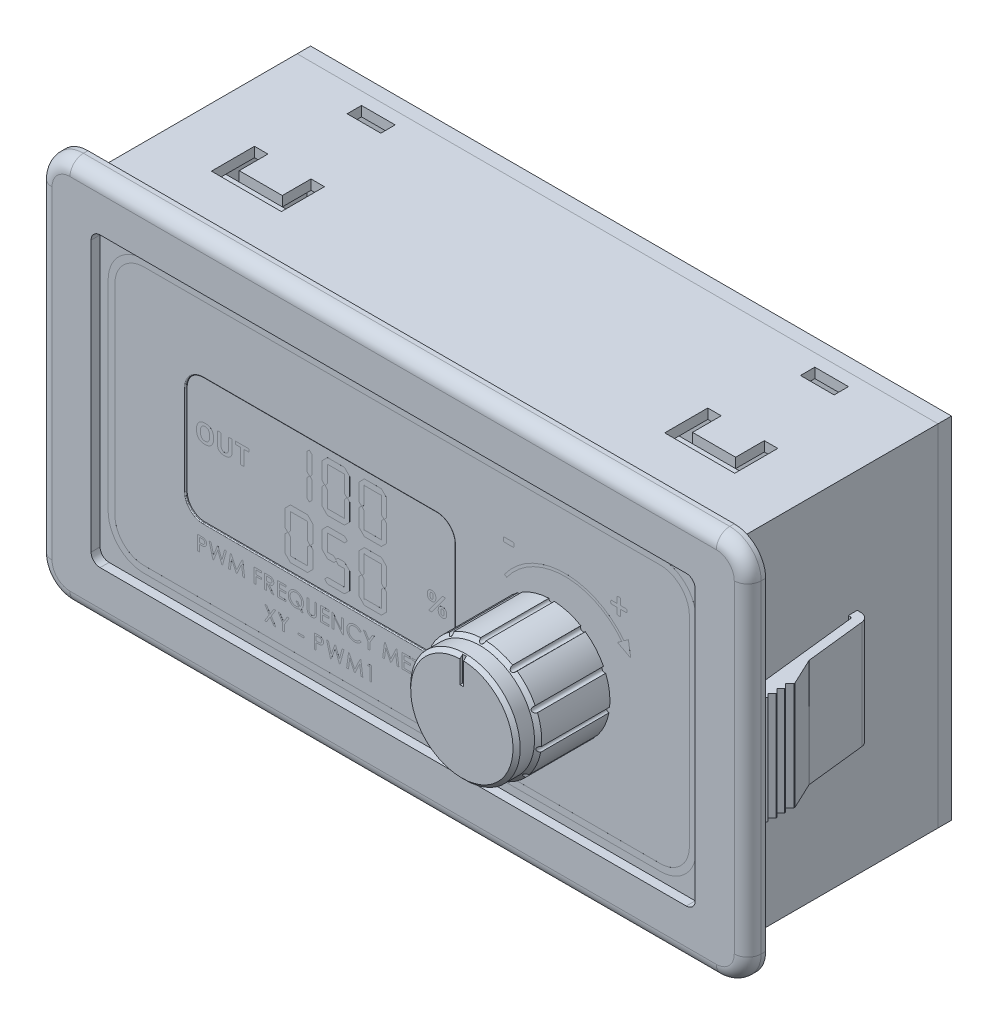
SolidWorks part; units mm, degrees
other "Case"
other "Back Cover"
other "PCB"
other "Rotary Encoder"
other "Connection"
material "ABS"
ref_plane "Front Plane" through (0, 0, 0) normal (0, 0, 1) x (1, 0, 0)
ref_plane "Top Plane" through (0, 0, 0) normal (0, 1, 0) x (1, 0, 0)
ref_plane "Right Plane" through (0, 0, 0) normal (1, 0, 0) x (0, 0, -1)
sketch "Sketch1" plane through (0, 0, 0) normal (0, 0, 1) x (1, 0, 0)
  line L1 (-39.5, 21.5) -> (39.5, 21.5)
  line L2 (-39.5, 21.5) -> (-39.5, -21.5)
  line L3 (-39.5, -21.5) -> (39.5, -21.5)
  line L4 (39.5, 21.5) -> (39.5, -21.5)
  line L5 (-39.5, 21.5) -> (39.5, -21.5) construction
  line L6 (-39.5, -21.5) -> (39.5, 21.5) construction
  point P0 (0, 0)
  dimension "D1" = 79
  dimension "D2" = 43
extrude "Boss-Extrude1" add sketch "Sketch1" along normal blind 2
sketch "Sketch2" plane through (0, 0, 0) normal (0, 0, -1) x (-1, 0, 0)
  line L1 (-35.7, 19.5) -> (35.7, 19.5)
  line L2 (-35.7, 19.5) -> (-35.7, -19.5)
  line L3 (-35.7, -19.5) -> (35.7, -19.5)
  line L4 (35.7, 19.5) -> (35.7, -19.5)
  line L5 (-35.7, 19.5) -> (35.7, -19.5) construction
  line L6 (-35.7, -19.5) -> (35.7, 19.5) construction
  point P0 (0, 0)
  dimension "D1" = 39
  dimension "D2" = 71.4
extrude "Boss-Extrude2" add sketch "Sketch2" along normal blind 23
sketch "Sketch3" plane through (0, 0, 2) normal (0, 0, 1) x (1, 0, 0)
  line L1 (-33.65, 16.05) -> (33.65, 16.05)
  line L2 (-33.65, 16.05) -> (-33.65, -16.05)
  line L3 (-33.65, -16.05) -> (33.65, -16.05)
  line L4 (33.65, 16.05) -> (33.65, -16.05)
  line L5 (-33.65, 16.05) -> (33.65, -16.05) construction
  line L6 (-33.65, -16.05) -> (33.65, 16.05) construction
  point P0 (0, 0)
  dimension "D1" = 67.3
  dimension "D2" = 32.1
extrude "Cut-Extrude1" cut sketch "Sketch3" against normal blind 1
sketch "Sketch4" plane through (0, 0, -23) normal (0, 0, -1) x (-1, 0, 0)
  line L0 (35.7, 19.5) -> (-35.7, 19.5) construction
  line L1 (-34.6, 18.4) -> (34.6, 18.4)
  line L2 (-34.6, 18.4) -> (-34.6, -18.4)
  line L3 (-34.6, -18.4) -> (34.6, -18.4)
  line L4 (34.6, 18.4) -> (34.6, -18.4)
  line L5 (-34.6, 18.4) -> (34.6, -18.4) construction
  line L6 (-34.6, -18.4) -> (34.6, 18.4) construction
  line L7 (-35.7, 19.5) -> (-35.7, -19.5) construction
  point P0 (0, 0)
  dimension "D1" = 1.1
  dimension "D2" = 1.1
extrude "Cut-Extrude2" cut sketch "Sketch4" against normal up to surface (23 mm away) up to face at (0, 0, 0)
sketch "Sketch5" plane through (0, 0, 1) normal (0, 0, 1) x (1, 0, 0)
  line L0 (0, 0) -> (18.15, 0) construction
  line L1 (18.15, 0) -> (33.65, 0) construction
  line L3 (33.65, -16.05) -> (33.65, 16.05) construction
  line L4 (33.65, 0) -> (39.5, 0) construction
  line L5 (39.5, -21.5) -> (39.5, 21.5) construction
  circle A0 centre (18.15, 0) radius 3.5
  dimension "D1" = 7
  dimension "D2" = 15.5
extrude "Cut-Extrude3" cut sketch "Sketch5" against normal up to surface (1 mm away) up to face at (0, 0, 0)
sketch "Sketch6" plane through (0, -19.5, 0) normal (0, -1, 0) x (1, 0, 0)
  line L0 (0, 0) -> (0, -8.5) construction
  line L1 (35.7, -23) -> (-35.7, -23) construction
  line L2 (-8.6, -8.5) -> (8.6, -8.5)
  line L3 (-11.1, -11) -> (-11.1, -23)
  line L4 (-11.1, -23) -> (11.1, -23)
  line L5 (11.1, -11) -> (11.1, -23)
  line L6 (-25.25, 0) -> (25.25, 0) construction
  line L7 (35.7, 0) -> (-35.7, 0) construction
  line L8 (25.25, 0) -> (25.25, -6.9) construction
  line L9 (-25.25, 0) -> (-25.25, -6.9) construction
  line L10 (21.35, -6.9) -> (29.15, -6.9)
  line L11 (-29.15, -6.9) -> (-21.35, -6.9)
  line L12 (-25.25, -6.9) -> (-25.25, -8.5) construction
  line L13 (25.25, -6.9) -> (25.25, -8.5) construction
  line L14 (22.85, -8.5) -> (27.65, -8.5)
  line L15 (-27.65, -8.5) -> (-22.85, -8.5)
  line L16 (-29.15, -6.9) -> (-29.15, -11.7)
  line L17 (-29.15, -11.7) -> (-27.65, -11.7)
  line L18 (-27.65, -11.7) -> (-27.65, -8.5)
  line L19 (-22.85, -8.5) -> (-22.85, -11.7)
  line L20 (-22.85, -11.7) -> (-21.35, -11.7)
  line L21 (-21.35, -11.7) -> (-21.35, -6.9)
  line L22 (29.15, -6.9) -> (29.15, -11.7)
  line L23 (29.15, -11.7) -> (27.65, -11.7)
  line L24 (27.65, -11.7) -> (27.65, -8.5)
  line L25 (22.85, -8.5) -> (22.85, -11.7)
  line L26 (22.85, -11.7) -> (21.35, -11.7)
  line L27 (21.35, -11.7) -> (21.35, -6.9)
  line L28 (-25.25, -8.5) -> (-25.25, -20.8) construction
  line L29 (-25.25, -20.8) -> (-25.25, -23) construction
  line L30 (-27.125, -20) -> (-23.375, -20)
  line L31 (-27.125, -20) -> (-27.125, -21.6)
  line L32 (-27.125, -21.6) -> (-23.375, -21.6)
  line L33 (-23.375, -20) -> (-23.375, -21.6)
  line L34 (-27.125, -20) -> (-23.375, -21.6) construction
  line L35 (-27.125, -21.6) -> (-23.375, -20) construction
  line L36 (25.25, -8.5) -> (25.25, -20.8) construction
  line L37 (25.25, -20.8) -> (25.25, -23) construction
  line L39 (23.375, -20) -> (27.125, -20)
  line L40 (23.375, -20) -> (23.375, -21.6)
  line L41 (23.375, -21.6) -> (27.125, -21.6)
  line L42 (27.125, -20) -> (27.125, -21.6)
  line L43 (23.375, -20) -> (27.125, -21.6) construction
  line L44 (23.375, -21.6) -> (27.125, -20) construction
  arc A0 (-8.6, -8.5) -> (-11.1, -11) centre (-8.6, -11) ccw
  arc A1 (8.6, -8.5) -> (11.1, -11) centre (8.6, -11) cw
  dimension "D3" = 2.5
  dimension "D1" = 22.2
  dimension "D2" = 8.5
  dimension "D4" = 50.5
  dimension "D6" = 4.8
  dimension "D7" = 7.8
  dimension "D8" = 1.6
  dimension "D9" = 4.8
  dimension "D10" = 3.75
  dimension "D11" = 1.6
  dimension "D12" = 3
extrude "Cut-Extrude4" cut sketch "Sketch6" against normal up to surface (1.1 mm away) up to face at (0, -18.4, -11.5)
sketch "Sketch7" plane through (0, 19.5, 0) normal (0, 1, 0) x (1, 0, 0)
  line L0 (21.35, 11.7) -> (21.35, 6.9) construction
  line L1 (22.85, 11.7) -> (21.35, 11.7) construction
  line L2 (22.85, 8.5) -> (22.85, 11.7) construction
  line L3 (29.15, 6.9) -> (29.15, 11.7) construction
  line L4 (29.15, 11.7) -> (27.65, 11.7) construction
  line L5 (27.65, 11.7) -> (27.65, 8.5) construction
  line L6 (22.85, 8.5) -> (27.65, 8.5) construction
  line L7 (21.35, 6.9) -> (29.15, 6.9) construction
  line L8 (21.35, 11.7) -> (21.35, 6.9)
  line L9 (22.85, 11.7) -> (21.35, 11.7)
  line L10 (22.85, 8.5) -> (22.85, 11.7)
  line L11 (29.15, 6.9) -> (29.15, 11.7)
  line L12 (29.15, 11.7) -> (27.65, 11.7)
  line L13 (27.65, 11.7) -> (27.65, 8.5)
  line L14 (22.85, 8.5) -> (27.65, 8.5)
  line L15 (21.35, 6.9) -> (29.15, 6.9)
  line L16 (-29.15, 11.7) -> (-27.65, 11.7) construction
  line L17 (-22.85, 11.7) -> (-21.35, 11.7) construction
  line L18 (-22.85, 8.5) -> (-22.85, 11.7) construction
  line L19 (-27.65, 11.7) -> (-27.65, 8.5) construction
  line L20 (-29.15, 6.9) -> (-29.15, 11.7) construction
  line L21 (-21.35, 11.7) -> (-21.35, 6.9) construction
  line L22 (-27.65, 8.5) -> (-22.85, 8.5) construction
  line L23 (-29.15, 6.9) -> (-21.35, 6.9) construction
  line L24 (-29.15, 11.7) -> (-27.65, 11.7)
  line L25 (-22.85, 11.7) -> (-21.35, 11.7)
  line L26 (-22.85, 8.5) -> (-22.85, 11.7)
  line L27 (-27.65, 11.7) -> (-27.65, 8.5)
  line L28 (-29.15, 6.9) -> (-29.15, 11.7)
  line L29 (-21.35, 11.7) -> (-21.35, 6.9)
  line L30 (-27.65, 8.5) -> (-22.85, 8.5)
  line L31 (-29.15, 6.9) -> (-21.35, 6.9)
  line L32 (-27.125, 20) -> (-27.125, 21.6) construction
  line L33 (-27.125, 20) -> (-23.375, 20) construction
  line L34 (-23.375, 20) -> (-23.375, 21.6) construction
  line L35 (-27.125, 21.6) -> (-23.375, 21.6) construction
  line L36 (-27.125, 20) -> (-27.125, 21.6)
  line L37 (-27.125, 20) -> (-23.375, 20)
  line L38 (-23.375, 20) -> (-23.375, 21.6)
  line L39 (-27.125, 21.6) -> (-23.375, 21.6)
  line L40 (23.375, 20) -> (23.375, 21.6) construction
  line L41 (23.375, 20) -> (27.125, 20) construction
  line L42 (27.125, 20) -> (27.125, 21.6) construction
  line L43 (23.375, 21.6) -> (27.125, 21.6) construction
  line L44 (23.375, 20) -> (23.375, 21.6)
  line L45 (23.375, 20) -> (27.125, 20)
  line L46 (27.125, 20) -> (27.125, 21.6)
  line L47 (23.375, 21.6) -> (27.125, 21.6)
extrude "Cut-Extrude5" cut sketch "Sketch7" against normal up to surface (1.1 mm away) up to face at (0, 18.4, -11.5)
sketch "Sketch8" plane through (0, 0, 0) normal (0, 1, 0) x (1, 0, 0)
  line L0 (0, 0) -> (0, 14) construction
  line L1 (-35.7, 14) -> (35.7, 14) construction
  line L2 (35.7, 23) -> (35.7, 0) construction
  line L3 (-35.7, 14) -> (-37, 14)
  line L4 (35.7, 14) -> (37, 14)
  line L5 (-35.7, 14) -> (-35.7, 13)
  line L6 (-35.7, 23) -> (-35.7, 0) construction
  line L7 (35.7, 14) -> (35.7, 13)
  line L8 (-35.7, 13) -> (-36.1054, 13)
  line L9 (35.7, 13) -> (36.1054, 13)
  line L10 (-36.1054, 13) -> (-37.5, 0.5)
  line L11 (-37.5, 0.5) -> (-39.25, 0.5)
  line L12 (-37.5, 0.5) -> (-37.5, 0) construction
  line L13 (39.5, 0) -> (-39.5, 0) construction
  line L14 (36.1054, 13) -> (37.5, 0.5)
  line L15 (37.5, 0.5) -> (37.5, 0) construction
  line L16 (-37.5, 0) -> (-35.7, 0) construction
  line L17 (37.5, 0) -> (35.7, 0) construction
  line L18 (37.5, 0.5) -> (39.25, 0.5)
  line L19 (-39.25, 0.5) -> (-39.25, 3.5)
  line L20 (-37, 14) -> (-37.8368, 6.5)
  line L21 (-37.8368, 6.5) -> (-39.25, 3.5)
  line L22 (39.25, 0.5) -> (39.25, 3.5)
  line L23 (37, 14) -> (37.8368, 6.5)
  line L24 (37.8368, 6.5) -> (39.25, 3.5)
  dimension "D1" = 14
  dimension "D2" = 74
  dimension "D3" = 1
  dimension "D4" = 0.5
  dimension "D5" = 75
  dimension "D6" = 3
  dimension "D7" = 6.5
  dimension "D8" = 6.5
  dimension "D9" = 78.5
  dimension "D10" = 1
extrude "Boss-Extrude3" add sketch "Sketch8" along normal mid plane 12
fillet "Fillet1" radius 1 2 edges at (37, 0, -14) (-37, 0, -14)
fillet "Fillet2" radius 0.2 6 edges at (36.1054, 0, -13) (-36.1054, 0, -13) (39.25, 0, -3.5) (37.8368, 0, -6.5) (-39.25, 0, -3.5) (-37.8368, 0, -6.5)
sketch "Sketch9" plane through (0, 6, 0) normal (0, 1, 0) x (1, 0, 0)
  line L0 (-39.25, 3.4553) -> (-38.7575, 2.9627)
  line L1 (-38.7575, 2.9627) -> (-39.25, 2.4702)
  line L2 (-39.25, 3.4553) -> (-39.25, 0.5) construction
  line L3 (-39.25, 2.4702) -> (-38.7575, 1.9776)
  line L4 (-38.7575, 1.9776) -> (-39.25, 1.4851)
  line L5 (-39.25, 1.4851) -> (-38.7575, 0.9925)
  line L6 (-38.7575, 0.9925) -> (-39.25, 0.5)
  line L7 (-39.25, 3.4553) -> (-40.25, 3.4553)
  line L8 (-40.25, 3.4553) -> (-40.25, 0.5)
  line L9 (-40.25, 0.5) -> (-39.25, 0.5)
  line L10 (-39.25, 0.5) -> (-37.5, 0.5) construction
  line L11 (-38.7575, 0.9925) -> (-39.25, 0.9925) construction
  line L12 (-39.25, 1.4851) -> (-39.25, 0.5) construction
  line L13 (39.25, 0.5) -> (40.25, 0.5)
  line L14 (40.25, 0.5) -> (40.25, 3.4553)
  line L15 (40.25, 3.4553) -> (39.25, 3.4553)
  line L16 (39.25, 0.5) -> (39.25, 1.4851) construction
  line L17 (39.25, 0.5) -> (39.25, 3.4553) construction
  line L18 (39.25, 0.9925) -> (38.7575, 0.9925) construction
  line L19 (39.25, 0.5) -> (38.7575, 0.9925)
  line L20 (38.7575, 0.9925) -> (39.25, 1.4851)
  line L21 (39.25, 1.4851) -> (38.7575, 1.9776)
  line L22 (38.7575, 1.9776) -> (39.25, 2.4702)
  line L23 (39.25, 2.4702) -> (38.7575, 2.9627)
  line L24 (38.7575, 2.9627) -> (39.25, 3.4553)
  line L25 (39.25, 2.4702) -> (39.25, 3.4553) construction
  line L26 (-39.25, 2.4702) -> (-39.25, 3.4553) construction
  dimension "D1" = 1
extrude "Cut-Extrude6" cut sketch "Sketch9" against normal up to surface (12 mm away) up to face at (-37.3148, -6, -8.43)
fillet "Fillet3" radius 0.1 8 edges at (39.25, 0, -3.4553) (39.25, 0, -2.4702) (39.25, 0, -1.4851) (39.25, 0, -0.5) (-39.25, 0, -3.4553) (-39.25, 0, -2.4702) (-39.25, 0, -1.4851) (-39.25, 0, -0.5)
sketch "Sketch10" plane through (0, 0, 1) normal (0, 0, 1) x (1, 0, 0)
  line L0 (5.85, 0) -> (-24.15, 0) construction
  line L1 (-22.15, 7) -> (3.85, 7)
  line L2 (-24.15, 5) -> (-24.15, -5)
  line L3 (-22.15, -7) -> (3.85, -7)
  line L4 (5.85, 5) -> (5.85, -5)
  line L5 (-24.15, 0) -> (-33.65, 0) construction
  line L6 (-33.65, 16.05) -> (-33.65, -16.05) construction
  arc A0 (-22.15, 7) -> (-24.15, 5) centre (-22.15, 5) ccw
  arc A1 (-24.15, -5) -> (-22.15, -7) centre (-22.15, -5) ccw
  arc A2 (3.85, -7) -> (5.85, -5) centre (3.85, -5) ccw
  arc A3 (3.85, 7) -> (5.85, 5) centre (3.85, 5) cw
  dimension "D4" = 2
  dimension "D1" = 14
  dimension "D2" = 30
  dimension "D3" = 9.5
extrude "Cut-Extrude7" cut sketch "Sketch10" against normal blind 0.2
fillet "Fillet4" radius 3.5 4 edges at (-39.5, 21.5, 1) (-39.5, -21.5, 1) (39.5, -21.5, 1) (39.5, 21.5, 1)
fillet "Fillet5" radius 1.5 8 edges at (38.4749, 20.4749, 2) (39.5, 0, 2) (38.4749, -20.4749, 2) (0, -21.5, 2) (-38.4749, -20.4749, 2) (-39.5, 0, 2) (-38.4749, 20.4749, 2) (0, 21.5, 2)
fillet "Fillet6" radius 1 4 edges at (-33.65, -16.05, 1.5) (33.65, -16.05, 1.5) (33.65, 16.05, 1.5) (-33.65, 16.05, 1.5)
fillet "Fillet7" radius 0.1 8 edges at (5.2642, 6.4142, 1) (5.85, 0, 1) (5.2642, -6.4142, 1) (-9.15, -7, 1) (-23.5642, -6.4142, 1) (-24.15, 0, 1) (-23.5642, 6.4142, 1) (-9.15, 7, 1)
sketch "Sketch12" plane through (0, 0, -23) normal (0, 0, -1) x (-1, 0, 0)
  line L1 (-35.7, 19.5) -> (35.7, 19.5)
  line L2 (-35.7, 19.5) -> (-35.7, -19.5)
  line L3 (-35.7, -19.5) -> (35.7, -19.5)
  line L4 (35.7, 19.5) -> (35.7, -19.5)
extrude "Boss-Extrude4" add sketch "Sketch12" along normal blind 1.5 separate body
sketch "Sketch14" plane through (0, 0, -24.5) normal (0, 0, -1) x (-1, 0, 0)
  line L0 (0, 0) -> (0, -11) construction
  line L1 (0, -11) -> (0, -19.5) construction
  line L2 (-35.7, -19.5) -> (35.7, -19.5) construction
  line L4 (-13.4, -11) -> (13.4, -11)
  line L5 (-16.4, -14) -> (-16.4, -19.5)
  line L6 (-16.4, -19.5) -> (16.4, -19.5)
  line L7 (16.4, -14) -> (16.4, -19.5)
  arc A0 (13.4, -11) -> (16.4, -14) centre (13.4, -14) cw
  arc A1 (-13.4, -11) -> (-16.4, -14) centre (-13.4, -14) ccw
  dimension "D3" = 3
  dimension "D1" = 32.8
  dimension "D2" = 8.5
extrude "Cut-Extrude8" cut sketch "Sketch14" against normal up to surface (1.5 mm away) up to face at (0, 0, -23)
sketch "Sketch15" plane through (0, -19.5, 0) normal (0, -1, 0) x (1, 0, 0)
  line L0 (0, 0) -> (0, -0.75) construction
  line L1 (35.7, 0) -> (-35.7, 0) construction
  line L2 (0, -0.75) -> (0, -7.75) construction
  line L3 (0, -7.75) -> (0, -8.5) construction
  line L4 (8.6, -8.5) -> (-8.6, -8.5) construction
  line L6 (-9.5, -0.75) -> (9.5, -0.75)
  line L7 (-11, -2.25) -> (-11, -6.25)
  line L8 (-9.5, -7.75) -> (9.5, -7.75)
  line L9 (11, -2.25) -> (11, -6.25)
  arc A0 (-9.5, -0.75) -> (-11, -2.25) centre (-9.5, -2.25) ccw
  arc A1 (-11, -6.25) -> (-9.5, -7.75) centre (-9.5, -6.25) ccw
  arc A2 (9.5, -7.75) -> (11, -6.25) centre (9.5, -6.25) ccw
  arc A3 (9.5, -0.75) -> (11, -2.25) centre (9.5, -2.25) cw
  dimension "D3" = 1.5
  dimension "D1" = 22
  dimension "D2" = 7
extrude "Boss-Extrude5" add sketch "Sketch15" along normal blind 0.01
sketch "Sketch16" plane through (0, -19.51, 0) normal (0, -1, 0) x (1, 0, 0)
  line L0 (11, -3.25) -> (10, -3.25) construction
  line L1 (11, -6.25) -> (11, -2.25) construction
  line L2 (10, -3.25) -> (6.5, -3.25) construction
  line L3 (6.5, -3.25) -> (2, -3.25) construction
  line L4 (2, -3.25) -> (-2.5, -3.25) construction
  line L5 (-2.5, -3.25) -> (-10, -3.25) construction
  line L6 (-10, -3.25) -> (-11, -3.25) construction
  line L7 (-11, -2.25) -> (-11, -6.25) construction
  line L8 (9.5, -0.75) -> (-9.5, -0.75) construction
  text T0 "V-" font "Calibri" height 2
  text T1 "V+" font "Calibri" height 2
  text T2 "PWM" font "Calibri" height 2
  dimension "D1" = 2.5
  dimension "D2" = 1
  dimension "D3" = 3.5
  dimension "D4" = 4.5
  dimension "D5" = 7.5
extrude "Boss-Extrude6" add sketch "Sketch16" along normal blind 0.001
sketch "Sketch17" plane through (0, -19.51, 0) normal (0, -1, 0) x (1, 0, 0)
  line L0 (-0.25, -7.75) -> (-0.25, -5.75) construction
  line L1 (-9.5, -7.75) -> (9.5, -7.75) construction
  line L2 (-0.4, -5.75) -> (-0.1, -5.75)
  line L3 (-11, -2.25) -> (-11, -6.25) construction
  line L4 (-0.25, -5.75) -> (-0.25, -4.45) construction
  line L5 (-1.625, -4.45) -> (1.125, -4.45)
  line L6 (-1.625, -4.45) -> (-1.625, -4.75)
  line L7 (-1.625, -4.75) -> (-0.4, -4.75)
  line L8 (-0.4, -4.75) -> (-0.4, -5.75)
  line L9 (1.125, -4.45) -> (1.125, -4.75)
  line L10 (1.125, -4.75) -> (-0.1, -4.75)
  line L11 (-0.1, -4.75) -> (-0.1, -5.75)
  line L12 (-0.25, -4.45) -> (-0.25, -3.9) construction
  line L13 (-0.25, -3.9) -> (-0.25, -3.2) construction
  line L15 (-1.25, -3.75) -> (0.75, -3.75)
  line L16 (-1.25, -3.75) -> (-1.25, -4.05)
  line L17 (-1.25, -4.05) -> (0.75, -4.05)
  line L18 (0.75, -3.75) -> (0.75, -4.05)
  line L19 (-1.25, -3.75) -> (0.75, -4.05) construction
  line L20 (-1.25, -4.05) -> (0.75, -3.75) construction
  line L21 (-0.875, -3.05) -> (0.375, -3.05)
  line L22 (-0.875, -3.05) -> (-0.875, -3.35)
  line L23 (-0.875, -3.35) -> (0.375, -3.35)
  line L24 (0.375, -3.05) -> (0.375, -3.35)
  line L25 (-0.875, -3.05) -> (0.375, -3.35) construction
  line L26 (-0.875, -3.35) -> (0.375, -3.05) construction
  dimension "D1" = 2
  dimension "D2" = 0.3
  dimension "D3" = 10.75
  dimension "D4" = 2.75
  dimension "D5" = 1
  dimension "D6" = 1.25
  dimension "D7" = 0.4
  dimension "D8" = 0.4
  dimension "D9" = 2
extrude "Boss-Extrude7" add sketch "Sketch17" along normal blind 0.001
sketch "Sketch18" plane through (0, 0, -6.9) normal (0, 0, -1) x (-1, 0, 0)
  line L4 (34.6, -18.4) -> (34.6, 18.4)
  line L5 (34.6, 18.4) -> (-34.6, 18.4)
  line L6 (-34.6, 18.4) -> (-34.6, -18.4)
  line L7 (-34.6, -18.4) -> (34.6, -18.4)
  line L8 (34.6, -18.4) -> (34.6, 18.4)
  line L9 (34.6, 18.4) -> (-34.6, 18.4)
  line L10 (-34.6, 18.4) -> (-34.6, -18.4)
  line L11 (-34.6, -18.4) -> (34.6, -18.4)
  circle A0 centre (-18.15, 0) radius 3.5 construction
  circle A1 centre (-18.15, 0) radius 3.5
  dimension "D1" = 0
extrude "Boss-Extrude8" add sketch "Sketch18" along normal blind 1.6 separate body
sketch "Sketch19" plane through (0, 0, -8.5) normal (0, 0, -1) x (-1, 0, 0)
  circle A0 centre (-18.15, 0) radius 9
  dimension "D1" = 18
extrude "Boss-Extrude9" add sketch "Sketch19" along normal blind 6 separate body
sketch "Sketch20" plane through (0, 0, -8.5) normal (0, 0, 1) x (1, 0, 0)
  circle A0 centre (18.15, 0) radius 3.25
  dimension "D1" = 6.5
extrude "Boss-Extrude11" add sketch "Sketch20" along normal up to surface (10.5 mm away) up to face at (0, 0, 2)
sketch "Sketch21" plane through (0, 0, 2) normal (0, 0, 1) x (1, 0, 0)
  circle A0 centre (18.15, 0) radius 1.5
  dimension "D1" = 3
extrude "Boss-Extrude12" add sketch "Sketch21" along normal blind 0.5
sketch "Sketch22" plane through (0, 0, 2.5) normal (0, 0, 1) x (1, 0, 0)
  circle A0 centre (18.15, 0) radius 6.5
  dimension "D1" = 13
extrude "Boss-Extrude13" add sketch "Sketch22" along normal blind 8
sketch "Sketch24" plane through (0, 0, 10.5) normal (0, 0, 1) x (1, 0, 0)
  circle A0 centre (18.15, 0) radius 6.1
  dimension "D1" = 12.2
extrude "Boss-Extrude14" add sketch "Sketch24" along normal blind 2
chamfer "Chamfer1" distance 0.4 angle 45 2 edges at (24.65, 0, 10.5) (24.25, 0, 12.5)
sketch "Sketch25" plane through (0, 0, 2.5) normal (0, 0, -1) x (-1, 0, 0)
  line L0 (-18.15, 0) -> (-18.15, 6.5) construction
  circle A0 centre (-18.15, 0) radius 6.5 construction
  circle A1 centre (-18.15, 6.5) radius 0.3
  dimension "D1" = 0.6
extrude "Cut-Extrude9" cut sketch "Sketch25" against normal up to surface (10 mm away) up to face at (23.85, 0, 12.5)
pattern_circular "CirPattern1" count 11 over 360 about axis through (18.15, 0, 10.5) along (0, 0, -1) of "Cut-Extrude9"
sketch "Sketch26" plane through (0, 0, 12.5) normal (0, 0, 1) x (1, 0, 0)
  line L0 (18.15, 0) -> (18.15, 3.2) construction
  line L2 (17.95, 7.2) -> (18.35, 7.2)
  line L3 (17.95, 7.2) -> (17.95, 3.2)
  line L4 (17.95, 3.2) -> (18.35, 3.2)
  line L5 (18.35, 7.2) -> (18.35, 3.2)
  dimension "D1" = 0.4
  dimension "D2" = 3.2
  dimension "D3" = 4
extrude "Cut-Extrude10" cut sketch "Sketch26" against normal blind 0.3
fillet "Fillet9" radius 3 1 edges at (9.15, 0, -14.5)
sketch "Sketch27" plane through (0, 0, 1) normal (0, 0, 1) x (1, 0, 0)
  line L0 (-9.15, 0) -> (-9.15, -10) construction
  line L1 (5.85, 0) -> (-24.15, 0) construction
  line L2 (-24.15, -10) -> (5.85, -10) construction
  line L3 (-9.15, -10) -> (-9.15, -13) construction
  line L4 (-24.15, -13) -> (5.85, -13) construction
  text T0 "PWM FREQUENCY METER" font "Century Gothic" height 1.6
  text T1 "XY - PWM1" font "Century Gothic" height 1.6
  dimension "D1" = 30
  dimension "D2" = 10
  dimension "D3" = 13
extrude "Boss-Extrude15" add sketch "Sketch27" along normal blind 0.001
sketch "Sketch28" plane through (0, 0, 1) normal (0, 0, 1) x (1, 0, 0)
  line L0 (0, 15.15) -> (0, -15.15) construction
  line L1 (-28.75, 15.15) -> (28.75, 15.15)
  line L2 (-32.75, 11.15) -> (-32.75, -11.15)
  line L3 (-28.75, -15.15) -> (28.75, -15.15)
  line L4 (32.75, 11.15) -> (32.75, -11.15)
  line L5 (0, 15.15) -> (0, 16.05) construction
  line L6 (32.65, 16.05) -> (-32.65, 16.05) construction
  line L7 (0, 0) -> (-32.75, 0) construction
  line L8 (-32.75, 0) -> (-33.65, 0) construction
  line L9 (-33.65, 15.05) -> (-33.65, -15.05) construction
  arc A0 (-28.75, 15.15) -> (-32.75, 11.15) centre (-28.75, 11.15) ccw
  arc A1 (-32.75, -11.15) -> (-28.75, -15.15) centre (-28.75, -11.15) ccw
  arc A2 (28.75, -15.15) -> (32.75, -11.15) centre (28.75, -11.15) ccw
  arc A3 (28.75, 15.15) -> (32.75, 11.15) centre (28.75, 11.15) cw
  dimension "D1" = 4
  dimension "D2" = 65.5
extrude "Extrude-Thin1" add sketch "Sketch28" along normal blind 0.001 thin thin type one direction reverse wall 0.75
sketch "Sketch29" plane through (0, 0, 1) normal (0, 0, 1) x (1, 0, 0)
  circle A0 centre (18.15, 0) radius 8
  dimension "D1" = 16
extrude "Extrude-Thin2" add sketch "Sketch29" along normal blind 0.001 thin thin type one direction wall 0.3
sketch "Sketch30" plane through (0, 0, 1) normal (0, 0, 1) x (1, 0, 0)
  line L0 (18.15, 0) -> (11.65, 4.6637) construction
  line L1 (11.65, 4.6637) -> (24.65, 4.6637) construction
  line L2 (24.65, 4.6637) -> (18.15, 0) construction
  line L3 (24.65, 4.6637) -> (24.8937, 4.8386)
  line L4 (11.65, 4.6637) -> (11.4062, 4.8386)
  circle A0 centre (18.15, 0) radius 8 construction
  arc A1 (11.65, 4.6637) -> (24.65, 4.6637) centre (18.15, 0) ccw
  circle A2 centre (18.15, 0) radius 8.3 construction
  arc A3 (11.4062, 4.8386) -> (24.8937, 4.8386) centre (18.15, 0) ccw
  dimension "D1" = 13
extrude "Cut-Extrude12" cut sketch "Sketch30" along normal up to surface (0.001 mm away) up to face at (26.45, 0, 1.001)
sketch "Sketch31" plane through (0, 0, 1.001) normal (0, 0, 1) x (1, 0, 0)
  line L0 (24.7719, 4.7511) -> (25.4714, 3.7761) construction
  line L1 (24.8937, 4.8386) -> (24.65, 4.6637) construction
  line L2 (25.2064, 5.4321) -> (23.9876, 4.5577)
  line L3 (24.7719, 4.7511) -> (24.597, 4.9949) construction
  line L4 (25.2064, 5.4321) -> (25.4714, 3.7761)
  line L5 (25.4714, 3.7761) -> (23.9876, 4.5577)
  line L6 (24.8937, 4.8386) -> (24.65, 4.6637) construction
  line L7 (18.15, 0) -> (18.15, -5.7) construction
  line L8 (18.15, 0) -> (18.15, 7) construction
  line L9 (13.15, 7) -> (23.15, 7) construction
  line L10 (23.15, 7) -> (25.15, 7) construction
  line L11 (13.15, 7) -> (11.15, 7) construction
  arc A0 (17.95, 5.6965) -> (18.35, 5.6965) centre (18.15, 0) ccw construction
  text T0 "-" font "Calibri" height 3
  text T1 "+" font "Calibri" height 2.5
  dimension "D1" = 1.5
  dimension "D2" = 1.5
  dimension "D3" = 7
  dimension "D4" = 10
  dimension "D5" = 14
extrude "Boss-Extrude16" add sketch "Sketch31" against normal up to surface (0.001 mm away) up to face at (0, 0, 1)
sketch "Sketch34" plane through (0, 0, 0) normal (1, 0, 0) x (0, 0, -1)
  line L0 (8.5, -18.4) -> (8.5, -10.4)
  line L1 (8.5, -18.4) -> (15, -18.4)
  line L2 (11, -18.4) -> (23, -18.4) construction
  line L3 (15, -18.4) -> (18.5, -17.4)
  line L4 (18.5, -17.4) -> (18.5, -12.4)
  line L5 (18.5, -12.4) -> (16.5, -10.4)
  line L6 (16.5, -10.4) -> (8.5, -10.4)
  line L7 (18.5, -17.4) -> (18.5, -18.4) construction
  line L8 (18.5, -18.4) -> (15, -18.4) construction
  dimension "D1" = 8
  dimension "D2" = 1
  dimension "D3" = 5
  dimension "D4" = 3.5
  dimension "D5" = 10
  dimension "D6" = 135
extrude "Boss-Extrude17" add sketch "Sketch34" along normal mid plane 20 separate body
sketch "Sketch35" plane through (0, 0, -18.5) normal (0, 0, -1) x (-1, 0, 0)
  line L0 (0, 0) -> (0, -12.4) construction
  line L1 (-10, -12.4) -> (10, -12.4) construction
  line L2 (0, -12.4) -> (0, -12.9) construction
  line L3 (0, -12.9) -> (0, -16.9) construction
  line L4 (0, -16.9) -> (0, -17.4) construction
  line L5 (-10, -17.4) -> (10, -17.4) construction
  line L6 (0, -14.9) -> (5, -14.9) construction
  line L7 (-0.25, -12.9) -> (0.25, -12.9)
  line L8 (-0.25, -12.9) -> (-0.25, -16.9)
  line L9 (-0.25, -16.9) -> (0.25, -16.9)
  line L10 (0.25, -12.9) -> (0.25, -16.9)
  line L11 (0, -14.9) -> (-5, -14.9) construction
  line L12 (5, -14.9) -> (7.5, -14.9) construction
  line L13 (4.75, -12.9) -> (5.25, -12.9)
  line L14 (4.75, -12.9) -> (4.75, -16.9)
  line L15 (4.75, -16.9) -> (5.25, -16.9)
  line L16 (5.25, -12.9) -> (5.25, -16.9)
  line L17 (4.75, -12.9) -> (5.25, -16.9) construction
  line L18 (4.75, -16.9) -> (5.25, -12.9) construction
  line L19 (-5.25, -12.9) -> (-4.75, -12.9)
  line L20 (-5.25, -12.9) -> (-5.25, -16.9)
  line L21 (-5.25, -16.9) -> (-4.75, -16.9)
  line L22 (-4.75, -12.9) -> (-4.75, -16.9)
  line L23 (-5.25, -12.9) -> (-4.75, -16.9) construction
  line L24 (-5.25, -16.9) -> (-4.75, -12.9) construction
  line L25 (-5, -14.9) -> (-7.5, -14.9) construction
  circle A0 centre (2.5, -14.9) radius 1.7
  circle A1 centre (-2.5, -14.9) radius 1.7
  circle A2 centre (-7.5, -14.9) radius 1.7
  circle A3 centre (7.5, -14.9) radius 1.7
  dimension "D5" = 3.4
  dimension "D1" = 0.5
  dimension "D2" = 4
  dimension "D3" = 10
  dimension "D4" = 15
extrude "Cut-Extrude13" cut sketch "Sketch35" against normal blind 3
sketch "Sketch36" plane through (0, -18.4, 0) normal (0, -1, 0) x (1, 0, 0)
  line L0 (0, -15) -> (0, -8.5) construction
  line L1 (10, -15) -> (-10, -15) construction
  line L2 (10, -8.5) -> (-10, -8.5) construction
  line L3 (-2.5, -11.75) -> (2.5, -11.75) construction
  line L4 (2.5, -11.75) -> (7.5, -11.75) construction
  line L5 (-2.5, -11.75) -> (-7.5, -11.75) construction
  line L7 (0.4, -9.15) -> (4.6, -9.15)
  line L8 (0.4, -9.15) -> (0.4, -14.35)
  line L9 (0.4, -14.35) -> (4.6, -14.35)
  line L10 (4.6, -9.15) -> (4.6, -14.35)
  line L11 (0.4, -9.15) -> (4.6, -14.35) construction
  line L12 (0.4, -14.35) -> (4.6, -9.15) construction
  line L13 (5.4, -9.15) -> (9.6, -9.15)
  line L14 (5.4, -9.15) -> (5.4, -14.35)
  line L15 (5.4, -14.35) -> (9.6, -14.35)
  line L16 (9.6, -9.15) -> (9.6, -14.35)
  line L17 (5.4, -9.15) -> (9.6, -14.35) construction
  line L18 (5.4, -14.35) -> (9.6, -9.15) construction
  line L19 (-0.4, -9.15) -> (-4.6, -9.15)
  line L20 (-0.4, -9.15) -> (-0.4, -14.35)
  line L21 (-0.4, -14.35) -> (-4.6, -14.35)
  line L22 (-4.6, -9.15) -> (-4.6, -14.35)
  line L23 (-0.4, -9.15) -> (-4.6, -14.35) construction
  line L24 (-0.4, -14.35) -> (-4.6, -9.15) construction
  line L25 (-5.4, -9.15) -> (-9.6, -9.15)
  line L26 (-5.4, -9.15) -> (-5.4, -14.35)
  line L27 (-5.4, -14.35) -> (-9.6, -14.35)
  line L28 (-9.6, -9.15) -> (-9.6, -14.35)
  line L29 (-5.4, -9.15) -> (-9.6, -14.35) construction
  line L30 (-5.4, -14.35) -> (-9.6, -9.15) construction
  point P5 (0, -11.75)
  dimension "D1" = 5
  dimension "D2" = 4.2
  dimension "D3" = 5.2
extrude "Cut-Extrude14" cut sketch "Sketch36" against normal blind 7
sketch "Sketch37" plane through (0, 0, -15.5) normal (0, 0, -1) x (-1, 0, 0)
  circle A0 centre (-7.5, -14.9) radius 1.5
  circle A1 centre (-2.5, -14.9) radius 1.5
  circle A2 centre (2.5, -14.9) radius 1.5
  circle A3 centre (7.5, -14.9) radius 1.5
  dimension "D1" = 3
extrude "Boss-Extrude18" add sketch "Sketch37" along normal blind 2
sketch "Sketch38" plane through (0, 0, -17.5) normal (0, 0, -1) x (-1, 0, 0)
  line L1 (-9.05, -14.5) -> (-5.95, -14.5)
  line L2 (-9.05, -14.5) -> (-9.05, -15.3)
  line L3 (-9.05, -15.3) -> (-5.95, -15.3)
  line L4 (-5.95, -14.5) -> (-5.95, -15.3)
  line L5 (-9.05, -14.5) -> (-5.95, -15.3) construction
  line L6 (-9.05, -15.3) -> (-5.95, -14.5) construction
  line L7 (-4.05, -14.5) -> (-0.95, -14.5)
  line L8 (-4.05, -14.5) -> (-4.05, -15.3)
  line L9 (-4.05, -15.3) -> (-0.95, -15.3)
  line L10 (-0.95, -14.5) -> (-0.95, -15.3)
  line L11 (-4.05, -14.5) -> (-0.95, -15.3) construction
  line L12 (-4.05, -15.3) -> (-0.95, -14.5) construction
  line L13 (0.95, -14.5) -> (4.05, -14.5)
  line L14 (0.95, -14.5) -> (0.95, -15.3)
  line L15 (0.95, -15.3) -> (4.05, -15.3)
  line L16 (4.05, -14.5) -> (4.05, -15.3)
  line L17 (0.95, -14.5) -> (4.05, -15.3) construction
  line L18 (0.95, -15.3) -> (4.05, -14.5) construction
  line L19 (5.95, -14.5) -> (9.05, -14.5)
  line L20 (5.95, -14.5) -> (5.95, -15.3)
  line L21 (5.95, -15.3) -> (9.05, -15.3)
  line L22 (9.05, -14.5) -> (9.05, -15.3)
  line L23 (5.95, -14.5) -> (9.05, -15.3) construction
  line L24 (5.95, -15.3) -> (9.05, -14.5) construction
  point P0 (-7.5, -14.9)
  point P5 (-2.5, -14.9)
  point P11 (2.5, -14.9)
  point P17 (7.5, -14.9)
  dimension "D1" = 3.1
  dimension "D2" = 0.8
extrude "Cut-Extrude15" cut sketch "Sketch38" against normal blind 1
sketch "Sketch39" plane through (0, -11.4, 0) normal (0, -1, 0) x (1, 0, 0)
  line L0 (-7.5, -9.15) -> (-7.5, -9.25) construction
  line L1 (-5.4, -9.15) -> (-9.6, -9.15) construction
  line L2 (-7.5, -9.25) -> (-7.5, -11.25) construction
  line L3 (-7.5, -11.25) -> (-7.5, -14.25) construction
  line L4 (-7.5, -14.25) -> (-7.5, -14.35) construction
  line L5 (-9.6, -14.35) -> (-5.4, -14.35) construction
  line L7 (-9.5, -9.25) -> (-5.5, -9.25)
  line L8 (-9.5, -9.25) -> (-9.5, -14.25)
  line L9 (-9.5, -14.25) -> (-5.5, -14.25)
  line L10 (-5.5, -9.25) -> (-5.5, -14.25)
  circle A0 centre (-7.5, -11.25) radius 1.5
  dimension "D4" = 3
  dimension "D1" = 4
  dimension "D2" = 5
  dimension "D3" = 2
extrude "Boss-Extrude19" add sketch "Sketch39" along normal blind 6.5
sketch "Sketch40" plane through (0, -18.4, 0) normal (0, -1, 0) x (1, 0, 0)
  line L0 (-7.5, -14.25) -> (-7.5, -12.05) construction
  line L1 (-9.5, -14.25) -> (-5.5, -14.25) construction
  line L3 (-8.5, -12.05) -> (-6.5, -12.05)
  line L4 (-8.5, -12.05) -> (-8.5, -14.25)
  line L5 (-8.5, -14.25) -> (-6.5, -14.25)
  line L6 (-6.5, -12.05) -> (-6.5, -14.25)
  dimension "D1" = 2.2
  dimension "D2" = 2
extrude "Boss-Extrude20" add sketch "Sketch40" against normal blind 3
fillet "Fillet8" radius 0.5 2 edges at (-7.5, -18.4, -12.05) (-7.5, -15.4, -12.05)
pattern_linear "LPattern1" count 4 spacing 5 along (1, 0, 0) of "Boss-Extrude19", "Boss-Extrude20", "Fillet8"
sketch "Sketch41" plane through (0, 0, 0.8) normal (0, 0, 1) x (1, 0, 0)
  line L0 (-18.2269, -7) -> (-18.2269, 0.5) construction
  line L1 (-22.15, -7) -> (3.85, -7) construction
  line L2 (-23.2269, 0.5) -> (-13.2269, 0.5) construction
  line L3 (-0.3465, -7) -> (-0.3465, -3) construction
  line L4 (-0.3465, -3) -> (4.85, -3) construction
  line L5 (4.85, -3) -> (5.85, -3) construction
  line L6 (5.85, -5) -> (5.85, 5) construction
  text T0 "OUT" font "Calibri" height 2
  text T1 "%" font "Calibri" height 2
  dimension "D1" = 4
  dimension "D2" = 1
  dimension "D3" = 10
  dimension "D4" = 7.5
  dimension "D5" = 18
extrude "Boss-Extrude21" add sketch "Sketch41" along normal blind 0.001
sketch "Sketch42" plane through (0, 0, 0.8) normal (0, 0, 1) x (1, 0, 0)
  line L0 (-15.7748, 0.5318) -> (-1.7073, 0.5318) construction
  line L1 (-15.7748, 0.5318) -> (-15.7748, -6.0947) construction
  line L2 (-15.7748, -6.0947) -> (-1.7073, -6.0947) construction
  line L3 (-1.7073, -6.0947) -> (-1.7073, 0.5318) construction
  text T0 "100" font "Digital Readout Thick Upright" height 4.5
  text T1 "050" font "Digital Readout Thick Upright" height 4.5
  point P5 (-1.7767, -6.1988)
  point P6 (-1.8809, 0.2117)
  point P7 (-1.7073, 0.5318)
  point P8 (-1.7073, -6.0947)
extrude "Boss-Extrude22" add sketch "Sketch42" along normal blind 0.001
